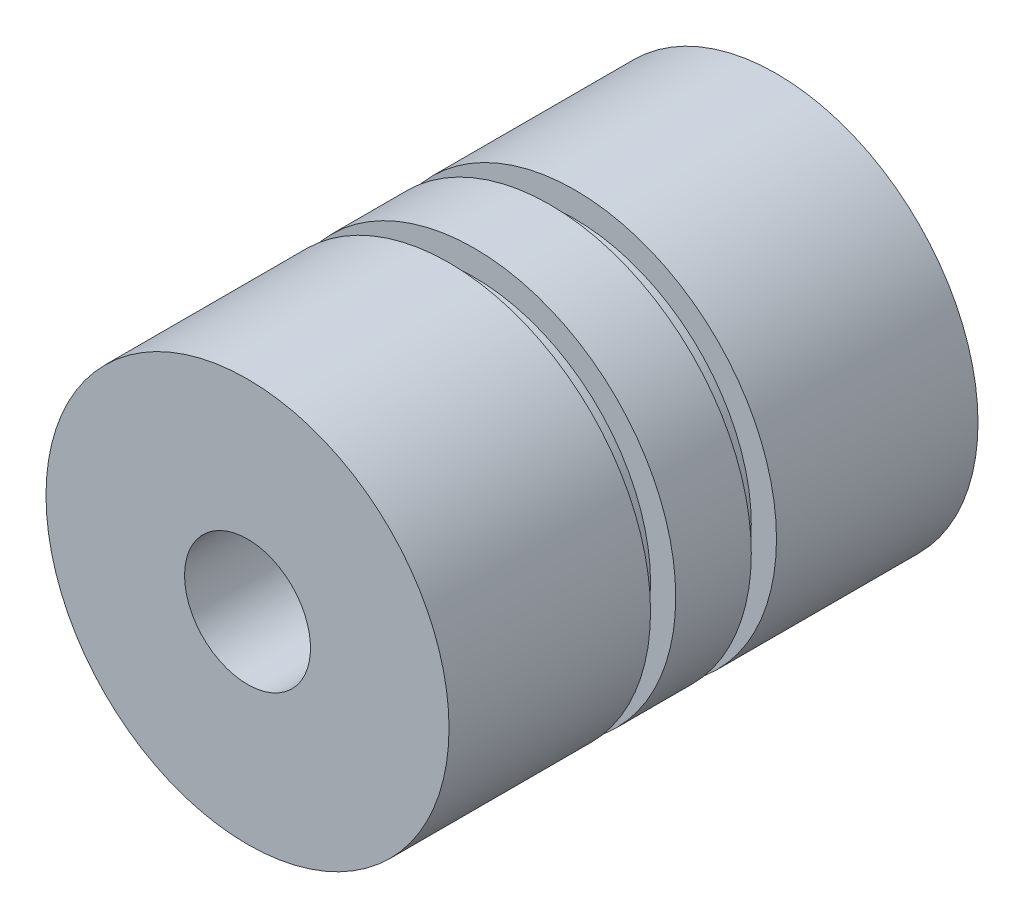
SolidWorks part; units mm, degrees
ref_plane "정면" through (0, 0, 0) normal (0, 0, 1) x (1, 0, 0)
ref_plane "윗면" through (0, 0, 0) normal (0, 1, 0) x (1, 0, 0)
ref_plane "우측면" through (0, 0, 0) normal (1, 0, 0) x (0, 0, -1)
sketch "스케치1" plane through (0, 0, 0) normal (0, 0, 1) x (1, 0, 0)
  circle A0 centre (0, 0) radius 16
  circle A1 centre (0, 0) radius 5
  dimension "D1" = 32
  dimension "D2" = 10
extrude "보스-돌출1" add sketch "스케치1" along normal mid plane 42
sketch "스케치2" plane through (0, 0, -21) normal (0, 0, -1) x (-1, 0, 0)
  circle A0 centre (0, 0) radius 7
  dimension "D1" = 14
extrude "컷-돌출1" cut sketch "스케치2" against normal blind 30
sketch "스케치3" plane through (0, 0, 0) normal (0, 0, 1) x (1, 0, 0)
  circle A0 centre (0, 0) radius 14
  circle A1 centre (0, 0) radius 16
  circle A2 centre (0, 0) radius 16 construction
  dimension "D1" = 28
extrude "컷-돌출3" cut sketch "스케치3" against normal blind 2 from offset 5
extrude "컷-돌출4" cut sketch "스케치3<2>" against normal blind 2 from offset 3
sketch "스케치3<2>" plane through (0, 0, 0) normal (0, 0, 1) x (1, 0, 0) same geometry as "스케치3"
